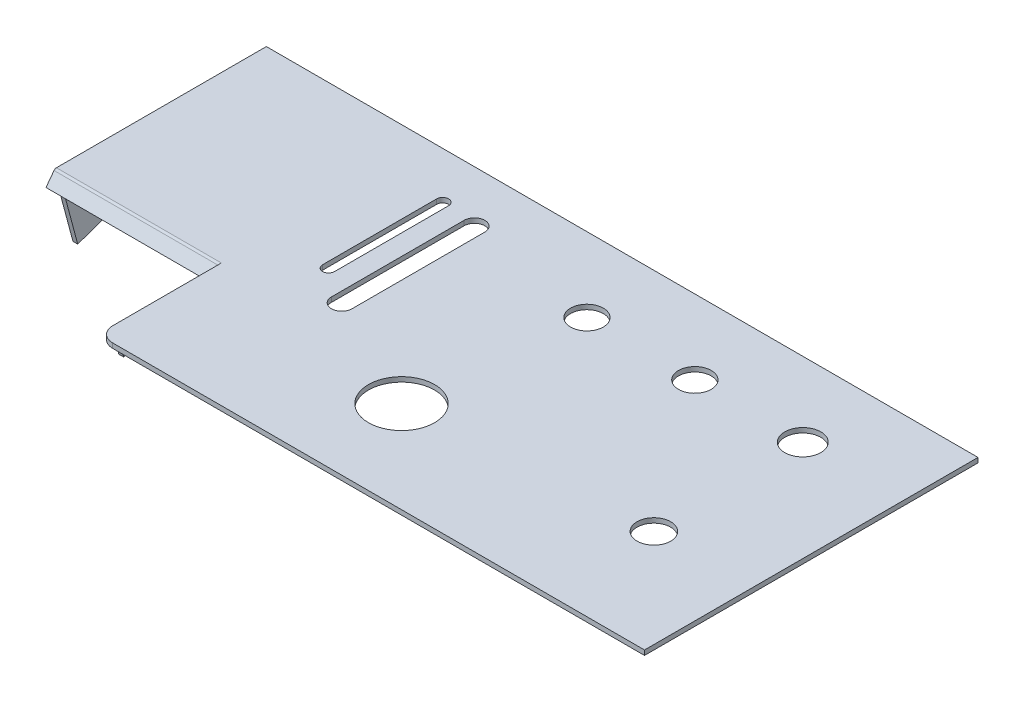
SolidWorks part; units mm, degrees
ref_plane "Front Plane" through (0, 0, 0) normal (0, 0, 1) x (1, 0, 0)
ref_plane "Top Plane" through (0, 0, 0) normal (0, 1, 0) x (1, 0, 0)
ref_plane "Right Plane" through (0, 0, 0) normal (1, 0, 0) x (0, 0, -1)
sketch "Sketch1" plane through (0, 0, 0) normal (0, 1, 0) x (1, 0, 0)
  line L0 (-101.3722, -12.5155) -> (-44.3722, -12.5155) construction
  line L1 (-44.3722, -53.5155) -> (137.6278, -53.5155) construction
  line L2 (-101.3722, -12.5155) -> (-101.3722, 58.4845) construction
  line L3 (-101.3722, 58.4845) -> (137.6278, 58.4845) construction
  line L4 (137.6278, -53.5155) -> (137.6278, 58.4845) construction
  line L5 (-44.3722, -12.5155) -> (-44.3722, -53.5155) construction
  line L6 (-26.4722, 42.7845) -> (-26.4722, 4.4845) construction
  line L7 (-23.4722, 42.7845) -> (-23.4722, 4.4845) construction
  line L8 (-29.4722, 42.7845) -> (-29.4722, 4.4845) construction
  line L9 (-14.1722, 41.1845) -> (-14.1722, -3.4155) construction
  line L10 (-9.5722, 41.1845) -> (-9.5722, -3.4155) construction
  line L11 (-18.7722, 41.1845) -> (-18.7722, -3.4155) construction
  line L12 (-26.4722, 45.7845) -> (-43.4588, 45.7845) construction
  line L13 (-26.4722, 1.4845) -> (-43.4588, 1.4845) construction
  line L14 (-14.1722, -8.0155) -> (-3.3024, -8.0155) construction
  line L15 (-14.1722, 45.7845) -> (0, 45.7845) construction
  line L16 (31.286, 33.4845) -> (122.5273, 33.4845) construction
  arc A0 (-23.4722, 42.7845) -> (-29.4722, 42.7845) centre (-26.4722, 42.7845) ccw construction
  arc A1 (-29.4722, 4.4845) -> (-23.4722, 4.4845) centre (-26.4722, 4.4845) ccw construction
  arc A2 (-9.5722, 41.1845) -> (-18.7722, 41.1845) centre (-14.1722, 41.1845) ccw construction
  arc A3 (-18.7722, -3.4155) -> (-9.5722, -3.4155) centre (-14.1722, -3.4155) ccw construction
  circle A7 centre (25.1778, -22.6655) radius 11.15 construction
  circle A8 centre (104.7278, -17.4655) radius 5.95 construction
  circle A9 centre (31.286, 33.4845) radius 6.25 construction
  circle A10 centre (67.536, 33.4845) radius 6.25 construction
  circle A11 centre (103.786, 33.4845) radius 6.25 construction
  point P0 (0, 0)
  point P10 (-26.4722, 23.6345)
  point P15 (-14.1722, 18.8845)
  dimension "D5" = 3
  dimension "D6" = 4.6
  dimension "D7" = 44.3
  dimension "D9" = 12.5
  dimension "D10" = 22.3
  dimension "D11" = 11.9
  dimension "D14" = 149.1
  dimension "D16" = 12.7
  dimension "D19" = 81.15
  dimension "D1" = 239
  dimension "D2" = 182
  dimension "D3" = 74.9
  dimension "D4" = 87.2
  dimension "D8" = 53.8
  dimension "D12" = 112
  dimension "D13" = 69.55
  dimension "D15" = 12.7
  dimension "D17" = 25
  dimension "D20" = 75.95
  dimension "D21" = 71
  dimension "D22" = 41
  dimension "D18" = 3
sketch "Sketch2" plane through (0, 0, 0) normal (0, 1, 0) x (1, 0, 0)
  line L0 (-101.3722, -12.5155) -> (-44.3722, -12.5155)
  line L1 (-101.3722, 58.4845) -> (137.6278, 58.4845)
  line L2 (-101.3722, 58.4845) -> (-101.3722, -12.5155)
  line L3 (-39.3722, -53.5155) -> (137.6278, -53.5155)
  line L4 (137.6278, 58.4845) -> (137.6278, -53.5155)
  line L5 (-44.3722, -12.5155) -> (-44.3722, -48.5155)
  line L6 (-26.4722, 4.4845) -> (-26.4722, 42.7845) construction
  line L7 (-28.4722, 4.4845) -> (-28.4722, 42.7845)
  line L8 (-24.4722, 4.4845) -> (-24.4722, 42.7845)
  line L9 (-14.1722, 41.1845) -> (-14.1722, -3.4155) construction
  line L10 (-10.7222, 41.1845) -> (-10.7222, -3.4155)
  line L11 (-17.6222, 41.1845) -> (-17.6222, -3.4155)
  arc A0 (-28.4722, 4.4845) -> (-24.4722, 4.4845) centre (-26.4722, 4.4845) ccw
  arc A1 (-24.4722, 42.7845) -> (-28.4722, 42.7845) centre (-26.4722, 42.7845) ccw
  arc A2 (-10.7222, 41.1845) -> (-17.6222, 41.1845) centre (-14.1722, 41.1845) ccw
  arc A3 (-17.6222, -3.4155) -> (-10.7222, -3.4155) centre (-14.1722, -3.4155) ccw
  circle A4 centre (31.286, 33.4845) radius 5.5
  circle A5 centre (67.536, 33.4845) radius 5.5
  circle A6 centre (103.786, 33.4845) radius 6.05
  circle A7 centre (25.1778, -22.6655) radius 11.1
  circle A8 centre (104.7278, -17.4655) radius 5.65
  arc A11 (-44.3722, -48.5155) -> (-39.3722, -53.5155) centre (-39.3722, -48.5155) ccw
  point P15 (-26.4722, 23.6345)
  point P24 (-14.1722, 18.8845)
  point P50 (-44.3722, -53.5155)
  dimension "D1" = 2
  dimension "D2" = 3.45
  dimension "D3" = 11
  dimension "D4" = 11
  dimension "D5" = 12.1
  dimension "D6" = 22.2
  dimension "D7" = 11.3
  dimension "D8" = 5
extrude "Boss-Extrude1" add sketch "Sketch2" along normal blind 1.6
sketch "Sketch3" plane through (-44.3722, 0, 0) normal (-1, 0, 0) x (0, 0, 1)
  line L0 (12.5155, 1.6) -> (15.5155, -2.4)
  line L1 (15.5155, -2.4) -> (12.5155, -2.4)
  line L2 (12.5155, -2.4) -> (12.5155, 1.6)
  dimension "D1" = 3
  dimension "D2" = 4
extrude "Boss-Extrude2" add sketch "Sketch3" along normal blind 57
fillet "Fillet1" radius 1 1 edges at (-72.8722, 1.6, 12.5155)
sketch "Sketch5" plane through (-101.3722, 0, 0) normal (-1, 0, 0) x (0, 0, 1)
  line L0 (-58.4845, 0) -> (12.5155, 0)
  line L3 (12.5155, 0) -> (6.4591, -22.6027)
  line L4 (6.4591, -22.6027) -> (-58.4845, 0)
  dimension "D1" = 23.4
  dimension "D2" = 71
  dimension "D3" = 75
extrude "Boss-Extrude3" add sketch "Sketch5" against normal blind 1.6
sketch "Sketch9" plane through (0, 1.6, 0) normal (0, 1, 0) x (1, 0, 0)
  line L0 (-44.3722, -12.0155) -> (-44.3722, -48.5155)
  line L2 (-45.9722, -48.5155) -> (-45.9722, -12.0155)
  line L3 (-101.3722, -12.0155) -> (-44.3722, -12.0155) construction
  line L4 (-45.9722, -12.0155) -> (-44.3722, -12.0155)
  line L6 (-40.9722, -53.5155) -> (-39.3722, -53.5155)
  arc A0 (-44.3722, -48.5155) -> (-39.3722, -53.5155) centre (-39.3722, -48.5155) ccw
  arc A1 (-45.9722, -48.5155) -> (-40.9722, -53.5155) centre (-40.9722, -48.5155) ccw
  dimension "D2" = 5
  dimension "D1" = 1.6
extrude "Boss-Extrude5" add sketch "Sketch9" against normal blind 1.6
sketch "Sketch10" plane through (-45.9722, 0, 0) normal (-1, 0, 0) x (0, 0, 1)
  line L0 (48.5155, 0) -> (46.4449, -7.7274)
  line L1 (46.4449, -7.7274) -> (11.5155, 0)
  line L2 (23.4155, 0) -> (11.5155, 0) construction
  line L3 (11.5155, 0) -> (48.5155, 0)
  dimension "D1" = 75
  dimension "D2" = 8
  dimension "D3" = 37
extrude "Boss-Extrude6" add sketch "Sketch10" against normal blind 1.6
